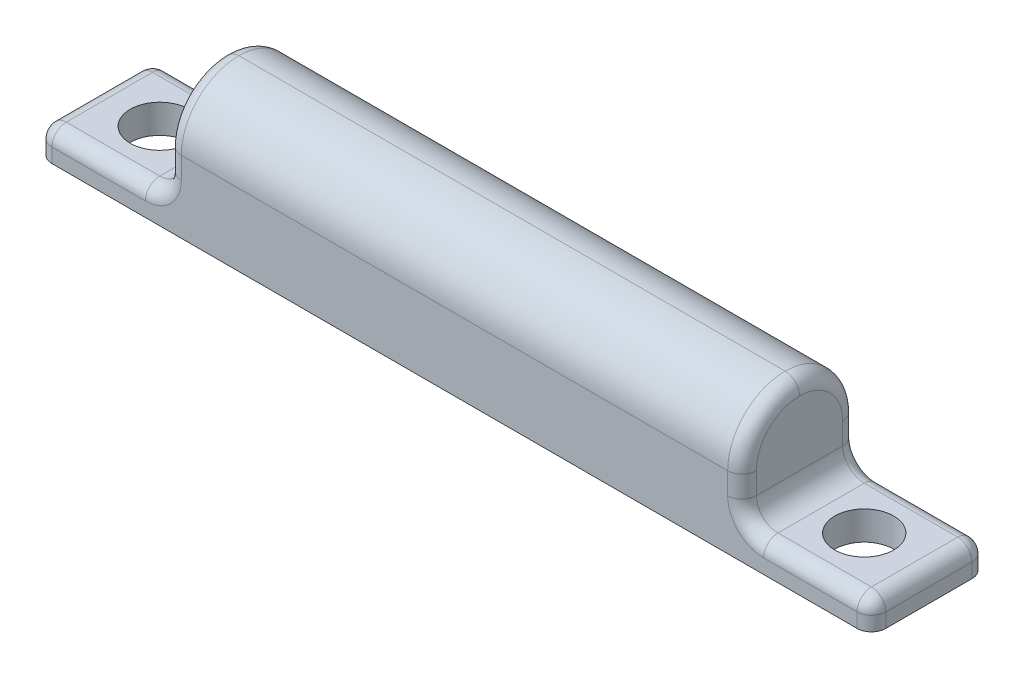
SolidWorks part; units mm, degrees
material "ABS"
ref_plane "Front Plane" through (0, 0, 0) normal (0, 0, 1) x (1, 0, 0)
ref_plane "Top Plane" through (0, 0, 0) normal (0, 1, 0) x (1, 0, 0)
ref_plane "Right Plane" through (0, 0, 0) normal (1, 0, 0) x (0, 0, -1)
sketch "Sketch1" plane through (0, 0, 0) normal (0, 1, 0) x (1, 0, 0)
  line L0 (0, -4) -> (58, -4) construction
  line L1 (0, 0) -> (58, 0)
  line L2 (0, 0) -> (0, -8)
  line L3 (0, -8) -> (58, -8)
  line L4 (58, 0) -> (58, -8)
  line L5 (29, 0) -> (29, -8) construction
  line L6 (9, 0) -> (9, -8)
  line L7 (49, 0) -> (49, -8)
  circle A0 centre (4.5, -4) radius 2.05
  circle A1 centre (53.5, -4) radius 2.05
  dimension "D3" = 4.1
  dimension "D1" = 58
  dimension "D2" = 8
  dimension "D4" = 4.5
  dimension "D5" = 4.5
  dimension "D6" = 9
  dimension "D7" = 9
extrude "Boss-Extrude1" add sketch "Sketch1" along normal blind 2 contours L7 L1 L6 L3 | L6 L1 L2 L3 A0 | L1 L7 L3 L4 A1 region at (4.5, 0, 0.1204) region at (29, 0, 4) region at (53.5, 0, 0.1204)
extrude "Boss-Extrude2" add sketch "Sketch1<3>" along normal blind 9 contours L7 L1 L6 L3 region at (29, 0, 4)
sketch "Sketch1<3>" plane through (0, 0, 0) normal (0, 1, 0) x (1, 0, 0) same geometry as "Sketch1"
fillet "Fillet1" radius 4 2 edges at (29, 9, 0) (29, 9, 8)
fillet "Fillet2" radius 1 4 edges at (58, 1, 0) (58, 1, 8) (0, 1, 0) (0, 1, 8)
fillet "Fillet4" radius 1.5 2 edges at (49, 2, 4) (9, 2, 4)
fillet "Fillet5" radius 1 22 edges at (9, 4.25, 8) (8.5607, 2.4393, 8) (4.25, 2, 8) (0.2929, 2, 7.7071) (0, 2, 4) (0.2929, 2, 0.2929) (4.25, 2, 0) (8.5607, 2.4393, 0) (9, 4.25, 0) (9, 7.8284, 1.1716) (9, 7.8284, 6.8284) (49, 7.8284, 1.1716) (49, 4.25, 0) (49.4393, 2.4393, 0) (53.75, 2, 0) (57.7071, 2, 0.2929) (58, 2, 4) (57.7071, 2, 7.7071) (53.75, 2, 8) (49.4393, 2.4393, 8) (49, 4.25, 8) (49, 7.8284, 6.8284)
equation "\"Width\"= 64mm"
equation "\"Height\" = 150mm"
equation "\"Depth\"= 90mm"
equation "\"D1@Sketch1\"=\"Width\"-6"
